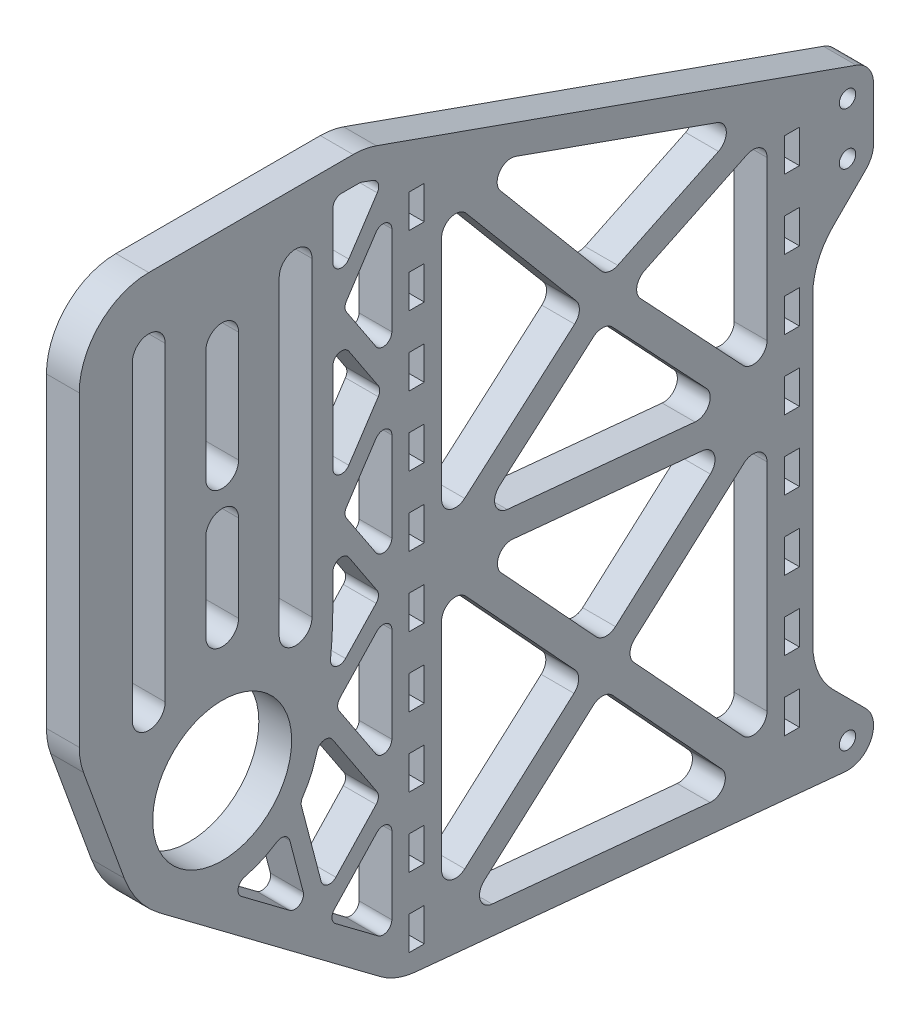
SolidWorks part; units mm, degrees
ref_plane "Front Plane" through (0, 0, 0) normal (0, 0, 1) x (1, 0, 0)
ref_plane "Top Plane" through (0, 0, 0) normal (0, 1, 0) x (1, 0, 0)
ref_plane "Right Plane" through (0, 0, 0) normal (1, 0, 0) x (0, 0, -1)
sketch "PlateGeometry" plane through (0, 0, 0) normal (1, 0, 0) x (0, 0, -1)
  line L1 (-38.1, -76.2) -> (38.1, -76.2) construction
  line L2 (-38.1, -76.2) -> (-38.1, 76.2) construction
  line L3 (-38.1, 76.2) -> (38.1, 76.2) construction
  line L4 (38.1, -76.2) -> (38.1, 76.2) construction
  line L5 (-38.1, -76.2) -> (38.1, 76.2) construction
  line L6 (-38.1, 76.2) -> (38.1, -76.2) construction
  line L11 (31.75, 76.2) -> (-31.75, 76.2) construction
  line L12 (31.75, 76.2) -> (31.75, -76.2) construction
  line L13 (31.75, -76.2) -> (-31.75, -76.2) construction
  line L14 (-31.75, 76.2) -> (-31.75, -76.2) construction
  line L15 (31.75, 76.2) -> (-31.75, -76.2) construction
  line L16 (31.75, -76.2) -> (-31.75, 76.2) construction
  point P0 (0, 0)
  point P9 (0, 0)
  line B0 (-35.7923, -66.6761) -> (-32.7923, -66.6739)
  line B1 (-35.7923, -66.6761) -> (-35.7877, -73.0261)
  line B2 (-35.7877, -73.0261) -> (-32.7877, -73.0239)
  line B3 (-32.7923, -66.6739) -> (-32.7877, -73.0239)
  line B4 (-35.7923, -66.6761) -> (-32.7877, -73.0239) construction
  line B5 (-35.7877, -73.0261) -> (-32.7923, -66.6739) construction
  line B6 (-35.7923, -53.9761) -> (-32.7923, -53.9739)
  line B7 (-35.7923, -53.9761) -> (-35.7877, -60.3261)
  line B8 (-35.7877, -60.3261) -> (-32.7877, -60.3239)
  line B9 (-32.7923, -53.9739) -> (-32.7877, -60.3239)
  line B10 (-35.7923, -53.9761) -> (-32.7877, -60.3239) construction
  line B11 (-35.7877, -60.3261) -> (-32.7923, -53.9739) construction
  line B12 (-35.7923, -41.2761) -> (-32.7923, -41.2739)
  line B13 (-35.7923, -41.2761) -> (-35.7877, -47.6261)
  line B14 (-35.7877, -47.6261) -> (-32.7877, -47.6239)
  line B15 (-32.7923, -41.2739) -> (-32.7877, -47.6239)
  line B16 (-35.7923, -41.2761) -> (-32.7877, -47.6239) construction
  line B17 (-35.7877, -47.6261) -> (-32.7923, -41.2739) construction
  line B18 (-35.7877, -34.9261) -> (-32.7877, -34.9239)
  line B19 (-32.7923, -28.5739) -> (-32.7877, -34.9239)
  line B20 (-35.7923, -15.8761) -> (-35.7877, -22.2261)
  line B21 (-35.7877, -22.2261) -> (-32.7877, -22.2239)
  line B22 (-32.7923, -15.8739) -> (-32.7877, -22.2239)
  line B23 (-35.7923, 9.5239) -> (-32.7923, 9.5261)
  line B24 (-32.7923, 9.5261) -> (-32.7877, 3.1761)
  line B25 (-35.7923, 9.5239) -> (-32.7877, 3.1761) construction
  line B26 (-35.7923, 22.2239) -> (-35.7877, 15.8739)
  line B27 (-35.7923, 34.9239) -> (-35.7877, 28.5739)
  line B28 (-35.7923, 47.6239) -> (-35.7877, 41.2739)
  line B29 (-35.7877, 41.2739) -> (-32.7923, 47.6261) construction
  line B30 (32.7886, -66.6757) -> (32.7914, -73.0257)
  line B31 (32.7914, -73.0257) -> (35.7914, -73.0243)
  line B32 (35.7886, -66.6743) -> (35.7914, -73.0243)
  line B33 (32.7886, -66.6757) -> (35.7914, -73.0243) construction
  line B34 (32.7914, -73.0257) -> (35.7886, -66.6743) construction
  line B35 (32.7886, -53.9757) -> (32.7914, -60.3257)
  line B36 (32.7914, -60.3257) -> (35.7914, -60.3243)
  line B37 (35.7886, -53.9743) -> (35.7914, -60.3243)
  line B38 (32.7886, -53.9757) -> (35.7914, -60.3243) construction
  line B39 (32.7914, -60.3257) -> (35.7886, -53.9743) construction
  line B40 (35.7886, -41.2743) -> (35.7914, -47.6243)
  line B41 (32.7914, -34.9257) -> (35.7914, -34.9243)
  line B42 (32.7886, -28.5757) -> (35.7914, -34.9243) construction
  line B43 (32.7886, -15.8757) -> (32.7914, -22.2257)
  line B44 (32.7886, -3.1757) -> (35.7914, -9.5243) construction
  line B45 (32.7914, -9.5257) -> (35.7886, -3.1743) construction
  line B46 (32.7886, 9.5243) -> (35.7886, 9.5257)
  line B47 (32.7886, 9.5243) -> (32.7914, 3.1743)
  line B48 (32.7914, 3.1743) -> (35.7914, 3.1757)
  line B49 (32.7886, 9.5243) -> (35.7914, 3.1757) construction
  line B50 (32.7886, 22.2243) -> (32.7914, 15.8743)
  line B51 (35.7886, 22.2257) -> (35.7914, 15.8757)
  line B52 (32.7886, 22.2243) -> (35.7914, 15.8757) construction
  line B53 (32.7914, 15.8743) -> (35.7886, 22.2257) construction
  line B54 (32.7914, 41.2743) -> (35.7914, 41.2757)
  line B55 (35.7886, 47.6257) -> (35.7914, 41.2757)
  line B56 (32.7886, 60.3243) -> (32.7914, 53.9743)
  line B57 (35.7886, 60.3257) -> (35.7914, 53.9757)
  line B58 (32.7886, 73.0243) -> (32.7914, 66.6743)
  line B59 (35.7886, 73.0257) -> (35.7914, 66.6757)
  line B60 (32.7914, 66.6743) -> (35.7886, 73.0257) construction
  circle B61 centre (-37.3063, -73.025) radius 5.5563 construction
  circle B62 centre (-37.3063, -73.025) radius 6.8263 construction
  circle B63 centre (-44.9262, -53.975) radius 5.5563 construction
  circle B64 centre (-44.9262, -53.975) radius 6.8263 construction
  dimension "D11" = 63.5
  dimension "D12" = 3.175
  dimension "D1" = 76.2
  dimension "D2" = 152.4
  dimension "D4" = 3.81
  dimension "D5" = 6.35
  dimension "D6" = 12.7
  dimension "D7" = 6.35
  dimension "D8" = 3.81
  dimension "D10" = 12.7
  dimension "D13" = 19.05
  dimension "D14" = 7.62
  dimension "D3" = 12
  dimension "D9" = 12
sketch_block_instance "SlotOutline-1"
sketch_block "SlotOutline" parameters "D1"=18.06, "D2"=7.2935
sketch_block_instance "SlotOutline-2"
sketch_block_instance "SlotOutline-3"
sketch_block_instance "SlotOutline-4"
sketch_block_instance "SlotOutline-5"
sketch_block_instance "SlotOutline-6"
sketch_block_instance "SlotOutline-7"
sketch_block_instance "SlotOutline-8"
sketch_block_instance "SlotOutline-9"
sketch_block_instance "SlotOutline-10"
sketch_block_instance "SlotOutline-11"
sketch_block_instance "SlotOutline-12"
sketch_block_instance "SlotOutline-13"
sketch_block_instance "SlotOutline-14"
sketch_block_instance "SlotOutline-15"
sketch_block_instance "SlotOutline-16"
sketch_block_instance "SlotOutline-17"
sketch_block_instance "SlotOutline-18"
sketch_block_instance "SlotOutline-19"
sketch_block_instance "SlotOutline-20"
sketch_block_instance "SlotOutline-21"
sketch_block_instance "SlotOutline-22"
sketch_block_instance "SlotOutline-23"
sketch_block_instance "SlotOutline-24"
sketch_block_instance "PulleyOutline-1"
sketch_block "PulleyOutline" parameters "D1"=11.1125, "D2"=13.6525
sketch_block_instance "PulleyOutline-2"
sketch "MotorGeometry" plane through (0, 0, 0) normal (1, 0, 0) x (0, 0, -1)
  line L0 (-83.2734, 1.775) -> (-83.2734, 49.025) construction
  line L3 (-50.2786, -55.4665) -> (-63.8121, -13.9087) construction
  line L4 (-41.2645, -76.9242) -> (-75.3216, -19.0975) construction
  line L5 (-38.1, -76.2) -> (-38.1, 76.2) construction
  line L6 (-38.1, -76.2) -> (38.1, -76.2) construction
  line L7 (38.1, -76.2) -> (38.1, 76.2) construction
  line L8 (-83.2734, 17.65) -> (-69.85, 9.9) construction
  line L9 (-69.85, 9.9) -> (-56.4266, 17.65) construction
  line L10 (-56.4266, 17.65) -> (-56.4266, 33.15) construction
  line L11 (-56.4266, 33.15) -> (-69.85, 40.9) construction
  line L12 (-69.85, 40.9) -> (-83.2734, 33.15) construction
  line L13 (-83.2734, 33.15) -> (-83.2734, 17.65) construction
  line L14 (-86.2734, 1.775) -> (-86.2734, 49.025)
  line L15 (-80.2734, 1.775) -> (-80.2734, 49.025)
  line L16 (-56.4266, 1.775) -> (-56.4266, 49.025) construction
  line L17 (-59.4266, 1.775) -> (-59.4266, 49.025)
  line L18 (-53.4266, 1.775) -> (-53.4266, 49.025)
  line L19 (-69.85, 8.3125) -> (-69.85, 47.25) construction
  line L20 (-72.85, 8.3125) -> (-72.85, 47.25)
  line L21 (-66.85, 8.3125) -> (-66.85, 47.25)
  circle A0 centre (44.45, -66.675) radius 1.5
  circle A1 centre (-69.85, -15.875) radius 11
  circle A5 centre (-69.85, -15.875) radius 30 construction
  circle A6 centre (-69.85, -15.875) radius 6.35 construction
  circle A7 centre (-44.9262, -53.975) radius 5.5562 construction
  circle A8 centre (-37.3063, -73.025) radius 5.5562 construction
  circle A9 centre (-69.85, -15.875) radius 25.5 construction
  circle A10 centre (-69.85, 25.4) radius 16 construction
  circle A11 centre (-69.85, 25.4) radius 11.5 construction
  circle A12 centre (-69.85, 25.4) radius 13.4234 construction
  arc A13 (-86.2734, 1.775) -> (-80.2734, 1.775) centre (-83.2734, 1.775) ccw
  arc A14 (-80.2734, 49.025) -> (-86.2734, 49.025) centre (-83.2734, 49.025) ccw
  arc A15 (-59.4266, 1.775) -> (-53.4266, 1.775) centre (-56.4266, 1.775) ccw
  arc A16 (-53.4266, 49.025) -> (-59.4266, 49.025) centre (-56.4266, 49.025) ccw
  arc A17 (-72.85, 8.3125) -> (-66.85, 8.3125) centre (-69.85, 8.3125) ccw
  arc A18 (-66.85, 47.25) -> (-72.85, 47.25) centre (-69.85, 47.25) ccw
  point P29 (-83.2734, 25.4)
  point P39 (-56.4266, 25.4)
  point P46 (-69.85, 27.7812)
  dimension "D1" = 22
  dimension "D4" = 60
  dimension "D5" = 12.7
  dimension "D7" = 4.5
  dimension "D8" = 32
  dimension "D9" = 4.5
  dimension "D13" = 3
  dimension "D3" = 6
  dimension "D2" = 31
  dimension "D6" = 38.1
  dimension "D10" = 31.75
  dimension "D11" = 9.525
  dimension "D12" = 6.35
  dimension "D14" = 15.875
  dimension "D15" = 1.5875
  dimension "D16" = 15.875
  dimension "D17" = 6.35
  dimension "D18" = 41.275
sketch "Sketch4" plane through (0, 0, 0) normal (1, 0, 0) x (0, 0, -1)
  line L0 (49.2125, 25.4) -> (49.2125, 34.925)
  line L1 (47.8176, 22.0324) -> (38.1, 12.3148)
  line L2 (-30.48, -50.8) -> (-38.1, -50.8) construction
  line L3 (-30.48, -50.8) -> (-30.48, -63.5) construction
  line L4 (-30.48, -63.5) -> (-38.1, -63.5) construction
  line L5 (-38.1, -50.8) -> (-38.1, -63.5) construction
  line L6 (-30.48, -50.8) -> (-38.1, -63.5) construction
  line L7 (-30.48, -63.5) -> (-38.1, -50.8) construction
  line L8 (38.1, 12.3148) -> (38.1, -53.5898)
  line L9 (38.1, -53.5898) -> (47.8176, -63.3074)
  line L10 (38.1, -76.2) -> (38.1, 76.2) construction
  line L11 (43.9929, -71.4155) -> (-38.1, -63.5)
  line L12 (-38.1, -63.5) -> (-81.28, -31.115)
  line L13 (-87.7511, -22.3905) -> (-95.9734, 0.2)
  line L14 (-95.9734, 0.2) -> (-95.9734, 71.25)
  line L15 (-43.7266, 71.25) -> (46.0419, 39.4136)
  line L16 (-95.9734, 71.25) -> (-43.7266, 71.25)
  line L17 (-83.2734, 1.775) -> (-83.2734, 58.55) construction
  line L18 (-86.2734, 1.775) -> (-86.2734, 58.55)
  line L19 (-80.2734, 1.775) -> (-80.2734, 58.55)
  line L20 (-69.85, 8.3125) -> (-69.85, 53.6) construction
  line L21 (-72.85, 8.3125) -> (-72.85, 53.6)
  line L22 (-66.85, 8.3125) -> (-66.85, 53.6)
  line L23 (-56.4266, 1.775) -> (-56.4266, 58.55) construction
  line L24 (-59.4266, 1.775) -> (-59.4266, 58.55)
  line L25 (-53.4266, 1.775) -> (-53.4266, 58.55)
  circle A0 centre (44.45, 25.4) radius 1.5
  circle A1 centre (44.45, 34.925) radius 1.5
  circle A2 centre (44.45, -66.675) radius 4.7625 construction
  circle A3 centre (44.45, 25.4) radius 4.7625 construction
  circle A4 centre (44.45, 34.925) radius 4.7625 construction
  circle A5 centre (-69.85, -15.875) radius 12.7
  arc A6 (43.9929, -71.4155) -> (47.8176, -63.3074) centre (44.45, -66.675) ccw
  circle A7 centre (-69.85, -15.875) radius 19.05
  arc A8 (47.8176, 22.0324) -> (49.2125, 25.4) centre (44.45, 25.4) ccw
  arc A9 (49.2125, 34.925) -> (46.0419, 39.4136) centre (44.45, 34.925) ccw
  circle A10 centre (44.45, -66.675) radius 1.5
  arc A11 (-86.2734, 1.775) -> (-80.2734, 1.775) centre (-83.2734, 1.775) ccw
  arc A12 (-80.2734, 58.55) -> (-86.2734, 58.55) centre (-83.2734, 58.55) ccw
  arc A13 (-72.85, 8.3125) -> (-66.85, 8.3125) centre (-69.85, 8.3125) ccw
  arc A14 (-66.85, 53.6) -> (-72.85, 53.6) centre (-69.85, 53.6) ccw
  arc A15 (-59.4266, 1.775) -> (-53.4266, 1.775) centre (-56.4266, 1.775) ccw
  arc A16 (-53.4266, 58.55) -> (-59.4266, 58.55) centre (-56.4266, 58.55) ccw
  arc A17 (-72.85, 24.1875) -> (-66.85, 24.1875) centre (-69.85, 24.1875) cw
  arc A18 (-72.85, 33.3625) -> (-66.85, 33.3625) centre (-69.85, 33.3625) ccw
  point P12 (-34.29, -57.15)
  point P36 (-83.2734, 30.1625)
  point P47 (-69.85, 30.9562)
  point P55 (-56.4266, 30.1625)
  point P71 (-95.9734, -0.5687)
  dimension "D1" = 3
  dimension "D4" = 9.525
  dimension "D9" = 25.4
  dimension "D10" = 38.1
  dimension "D11" = 6
  dimension "D14" = 3.175
  dimension "D2" = 9.525
  dimension "D3" = 101.6
  dimension "D5" = 3.81
  dimension "D6" = 12.7
  dimension "D7" = 45
  dimension "D8" = 45
  dimension "D12" = 12.7
  dimension "D13" = 25.4
  dimension "D15" = 15.875
  dimension "D16" = 12.7
  dimension "D17" = 12.7
  dimension "D18" = 20
  dimension "D19" = 12.7
extrude "Boss-Extrude1" add sketch "Sketch4" along normal mid plane 6 contours L0 A9 L13 A7 L12 L11 A6 L9 L8 L1 A8 A0 A1 | A7 A5 | A18 L21 A17 L22 region at (0, 1.9375, 18.512) region at (0, 2.355, 73.0644) region at (0, 28.775, 69.85)
sketch "Sketch5" plane through (3, 0, 0) normal (1, 0, 0) x (0, 0, -1)
  line B0 (35.665, -54.102) -> (32.915, -54.102)
  line B1 (35.665, -54.102) -> (35.665, -60.198)
  line B2 (35.665, -60.198) -> (32.915, -60.198)
  line B3 (32.915, -54.102) -> (32.915, -60.198)
  line B4 (35.665, -54.102) -> (32.915, -60.198) construction
  line B5 (35.665, -60.198) -> (32.915, -54.102) construction
  line B6 (-32.915, -54.102) -> (-35.665, -54.102)
  line B7 (-32.915, -54.102) -> (-32.915, -60.198)
  line B8 (-32.915, -60.198) -> (-35.665, -60.198)
  line B9 (-35.665, -54.102) -> (-35.665, -60.198)
  line B10 (-32.915, -54.102) -> (-35.665, -60.198) construction
  line B11 (-32.915, -60.198) -> (-35.665, -54.102) construction
sketch_block_instance "Slot-1"
sketch_block "Slot" parameters "D1"=11.2845, "D2"=5.6739
sketch_block_instance "Slot-2"
extrude "LowerSlot" cut sketch "Sketch5" against normal through all both and the other way through all contours B0 B3 B2 B1 region at (3, -57.15, -34.29)
extrude "UpperSlot" cut sketch "Sketch5<3>" against normal through all both and the other way through all contours B6 B9 B8 B7 region at (3, -57.15, 34.29)
sketch "Sketch5<3>" plane through (3, 0, 0) normal (1, 0, 0) x (0, 0, -1) same geometry as "Sketch5"
pattern_linear "LowerSlots" count 8 spacing 12.7 along (0, 1, 0) of "LowerSlot"
pattern_linear "LPattern2" count 10 spacing 12.7 along (0, 1, 0) of "UpperSlot"
sketch "Sketch6" plane through (3, 0, 0) normal (1, 0, 0) x (0, 0, -1)
  line L1 (-38.84, -56.595) -> (-38.84, 64.1269)
  line L2 (-49.6166, 1.775) -> (-49.6166, 58.55)
  line L3 (-49.6166, 1.775) -> (-49.6166, 58.55)
  line L4 (-29.74, 60.8996) -> (-29.74, -59.2025)
  line L5 (29.74, -64.9377) -> (29.74, 39.805)
  line L6 (32.915, -54.102) -> (32.915, -60.198) construction
  line L8 (-32.915, -54.102) -> (-32.915, -60.198) construction
  line L9 (-35.665, -54.102) -> (-35.665, -60.198) construction
  line L11 (-49.6166, 58.55) -> (-49.6166, 66.17)
  line L12 (29.74, -6.1471) -> (0, 25.5315) construction
  line L14 (29.74, -6.1471) -> (-29.74, -59.2025) construction
  line L15 (-29.74, -0.412) -> (29.74, -64.9377) construction
  line L16 (0, 25.5315) -> (-29.74, -0.412) construction
  line L17 (0, 25.5315) -> (-29.74, 60.8996) construction
  line L18 (0, 25.5315) -> (29.74, 39.805) construction
  line L19 (0, -32.6748) -> (0, 25.5315) construction
  line L20 (44.1325, 25.5315) -> (44.1325, 34.7007)
  line L21 (44.1325, 34.7007) -> (-44.6007, 66.17)
  line L22 (-44.6007, 66.17) -> (-90.8934, 66.17)
  line L23 (-90.8934, 66.17) -> (-90.8934, 1.0957)
  line L24 (-90.8934, 1.0957) -> (-82.9775, -20.653)
  line L25 (-78.232, -27.051) -> (-36.1929, -58.5803)
  line L26 (-36.1929, -58.5803) -> (43.6001, -66.2741)
  line L27 (43.6001, -66.2741) -> (33.02, -55.694)
  line L28 (33.02, -55.694) -> (33.02, 14.419)
  line L29 (33.02, 14.419) -> (44.1325, 25.5315)
  line L30 (44.1325, 25.5315) -> (44.1325, 34.7007)
  line L31 (44.1325, 34.7007) -> (-44.6007, 66.17)
  line L32 (-44.6007, 66.17) -> (-90.8934, 66.17)
  line L33 (-90.8934, 66.17) -> (-90.8934, 1.0957)
  line L34 (-90.8934, 1.0957) -> (-82.9775, -20.653)
  line L35 (-78.232, -27.051) -> (-36.1929, -58.5803)
  line L36 (-36.1929, -58.5803) -> (43.6001, -66.2741)
  line L37 (43.6001, -66.2741) -> (33.02, -55.694)
  line L38 (33.02, -55.694) -> (33.02, 14.419)
  line L39 (33.02, 14.419) -> (44.1325, 25.5315)
  line L40 (-29.74, -0.412) -> (29.74, -6.1471) construction
  line L41 (28.0492, -4.2516) -> (-31.4308, -57.307)
  line L42 (-31.6076, -2.1335) -> (27.8724, -66.6592)
  line L43 (-29.9838, -2.9402) -> (29.4962, -8.6754)
  line L44 (-1.6697, 27.4456) -> (-31.4097, 1.5021)
  line L45 (31.5918, -4.4086) -> (1.8518, 27.27)
  line L46 (1.099, 23.2416) -> (30.839, 37.5151)
  line L47 (1.9441, 27.1662) -> (-27.7959, 62.5343)
  line L48 (31.4308, -8.0426) -> (-28.0492, -61.098)
  line L49 (-27.8724, 1.3096) -> (31.6076, -63.2161)
  line L50 (-29.4962, 2.1163) -> (29.9838, -3.6188)
  line L51 (1.6697, 23.6174) -> (-28.0703, -2.326)
  line L52 (27.8882, -7.8856) -> (-1.8518, 23.793)
  line L53 (-1.099, 27.8214) -> (28.641, 42.0949)
  line L54 (-1.9441, 23.8968) -> (-31.6841, 59.2649)
  line L55 (-38.84, 64.1269) -> (-49.6166, 47.8087) construction
  line L56 (-49.6166, 47.8087) -> (-38.84, 31.4904) construction
  line L57 (-38.84, 31.4904) -> (-49.6166, 15.1721) construction
  line L58 (-49.6166, 15.1721) -> (-38.84, -1.1462) construction
  line L59 (-38.84, -1.1462) -> (-51.1968, -14.2943) construction
  line L60 (-51.1968, -14.2943) -> (-38.84, -33.0054) construction
  line L61 (-38.84, -33.0054) -> (-51.844, -46.842) construction
  line L62 (-51.844, -46.842) -> (-56.7923, -27.9425) construction
  line L63 (-49.6166, 47.8087) -> (-38.84, 47.8087) construction
  line L64 (-40.1647, 65.0018) -> (-51.519, 47.8087)
  line L65 (-51.519, 47.8087) -> (-40.7424, 31.4904)
  line L66 (-40.7424, 31.4904) -> (-51.519, 15.1721)
  line L67 (-51.519, 15.1721) -> (-40.8564, -0.9736)
  line L68 (-40.8564, -0.9736) -> (-53.2132, -14.1217)
  line L69 (-53.2132, -14.1217) -> (-40.8564, -32.8328)
  line L70 (-40.8564, -32.8328) -> (-51.0352, -43.6634)
  line L71 (-51.0352, -43.6634) -> (-55.8417, -25.3054)
  line L72 (-37.5153, 63.2521) -> (-47.7142, 47.8087)
  line L73 (-47.7142, 47.8087) -> (-36.9376, 31.4904)
  line L74 (-36.9376, 31.4904) -> (-47.7142, 15.1721)
  line L75 (-47.7142, 15.1721) -> (-36.8236, -1.3187)
  line L76 (-36.8236, -1.3187) -> (-49.1804, -14.4668)
  line L77 (-49.1804, -14.4668) -> (-36.8236, -33.1779)
  line L78 (-36.8236, -33.1779) -> (-52.6527, -50.0207)
  line L79 (-52.6527, -50.0207) -> (-58.328, -28.3446)
  line L80 (-51.0352, -43.6634) -> (-55.2566, -27.5404) construction
  arc A0 (-49.6166, 1.775) -> (-52.7441, -20.7242) centre (-132.1114, 1.775) cw
  circle A6 centre (-69.85, -15.875) radius 17.78
  circle A7 centre (-69.85, -15.875) radius 17.78
  arc A8 (-82.9775, -20.653) -> (-78.232, -27.051) centre (-69.85, -15.875) ccw
  arc A9 (-82.9775, -20.653) -> (-78.232, -27.051) centre (-69.85, -15.875) ccw
  point P22 (0, 0)
  point P73 (-38.84, -36.575)
  point P74 (-38.84, -1.1462)
  point P76 (-51.1968, -14.2943)
  point P95 (-55.8417, -25.3054)
  dimension "D4" = 3.175
  dimension "D5" = 3.175
  dimension "D6" = 3.175
  dimension "D9" = 3.175
  dimension "D1" = 5.08
  dimension "D2" = 5.08
  dimension "D3" = 3.81
  dimension "D7" = 2.54
  dimension "D8" = 2.54
extrude "Cut-Extrude1" cut sketch "Sketch6" against normal through all both and the other way through all contours L42 L4 L41 | L42 L48 L36 | L48 L49 L5 | L43 L49 L41 | L50 L52 L51 | L46 L45 L5 | L47 L53 L31 | L44 L54 L4 region at (3, -30.8188, 21.0325) region at (3, -53.4468, 0.174) region at (3, -13.6041, -0.174) region at (3, -34.5308, -21.0325) region at (3, 28.5725, 21.0098) region at (3, 6.862, 0.1757) region at (3, 19.7645, -21.2351) region at (3, 42.9661, -0.6765)
extrude "Cut-Extrude2" cut sketch "Sketch6<3>" against normal through all both and the other way through all contours A7 L35 L79 | L1 L78 L35 | A7 L71 L70 L69 A0 | L76 L77 L1 | L3 A0 L68 L67 | L74 L75 L1 | L66 L65 L3 | L72 L73 L1 | L64 L31 L32 L11 L3 region at (3, -46.5729, 42.7487) region at (3, -16.0186, 42.2868) region at (3, -36.4632, 60.1732) region at (3, 15.1721, 41.7981) region at (3, -30.5698, 49.1442) region at (3, 47.8087, 41.7981) region at (3, 0.0237, 46.8241) region at (3, 60.7684, 46.4548) region at (3, 31.4904, 46.6586)
sketch "Sketch6<3>" plane through (3, 0, 0) normal (1, 0, 0) x (0, 0, -1) same geometry as "Sketch6"
fillet "Fillet1" radius 2.54 24 edges at (0, 25.8059, 3.5493) (0, 56.953, 29.74) (0, 2.9587, 29.74) (0, 28.6736, -0.6765) (0, 41.0022, -26.3642) (0, 59.2225, 25.0112) (0, 24.742, -4.2252) (0, -2.4361, -29.74) (0, 36.9876, -29.74) (0, -2.972, -23.2753) (0, 22.0076, 0.1757) (0, 1.5504, 23.6266) (0, -29.116, -0.174) (0, -8.1179, -23.7147) (0, -32.8517, -3.6175) (0, -61.1901, -29.74) (0, -9.5507, -29.74) (0, -36.2336, 0.174) (0, -59.5346, 26.2964) (0, -64.5721, -25.9485) (0, -4.1595, 29.74) (0, -55.7989, 29.74) (0, -32.498, 3.6175) (0, -3.5782, 23.3668)
fillet "Fillet2" radius 1.5875 29 edges at (0, 64.6736, 40.3814) (0, 66.17, 49.6166) (0, 50.6894, 49.6166) (0, 47.8087, 47.7142) (0, 34.3711, 38.84) (0, 61.2462, 38.84) (0, 31.4904, 40.7424) (0, 44.9279, 49.6166) (0, 18.0528, 49.6166) (0, 15.1721, 47.7142) (0, 1.7346, 38.84) (0, 28.6097, 38.84) (0, -11.426, 50.6797) (0, -0.9736, 40.8564) (0, 12.2914, 49.6166) (0, -30.1246, 38.84) (0, -3.4642, 38.84) (0, -43.6634, 51.0352) (0, -32.8328, 40.8564) (0, -35.3234, 38.84) (0, -47.8004, 50.5661) (0, -56.595, 38.84) (0, -33.6501, 69.4332) (0, -45.3105, 53.886) (0, -29.2185, 58.0992) (0, -14.4668, 49.1804)
fillet "Fillet3" radius 12.7 6 edges at (0, -63.5, 38.1) (0, 71.25, 43.7266) (0, 71.25, 95.9734) (0, 0.2, 95.9734) (0, 12.3148, -38.1) (0, -53.5898, -38.1)
